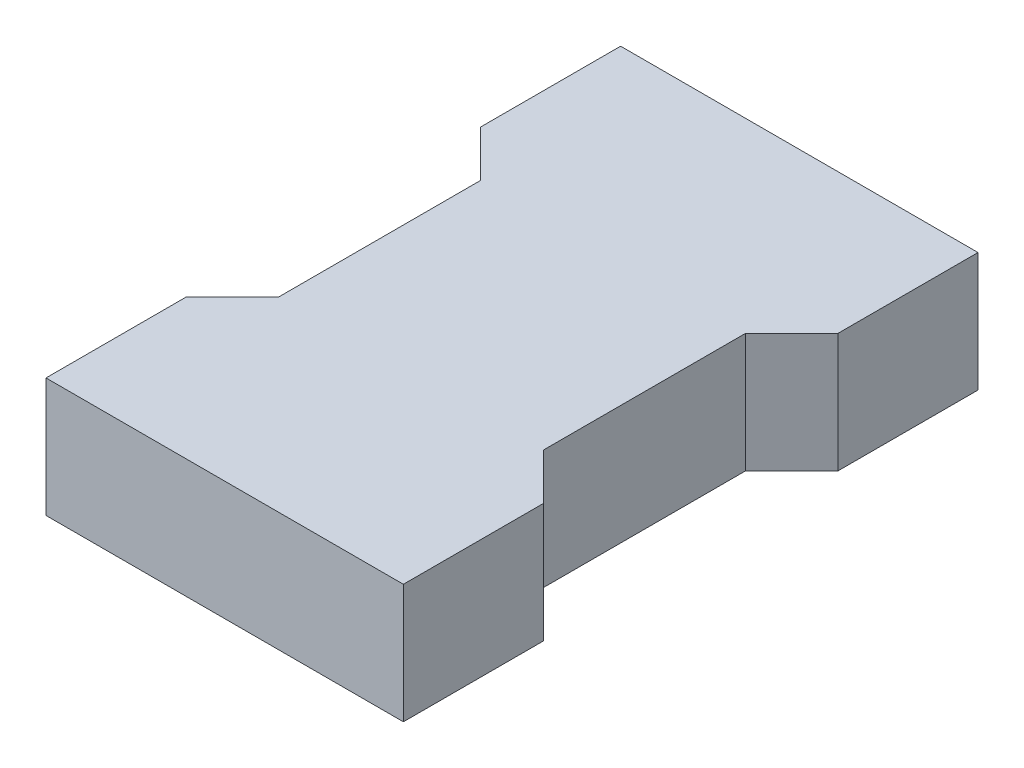
SolidWorks part; units mm, degrees
ref_plane "前视基准面" through (0, 0, 0) normal (0, 0, 1) x (1, 0, 0)
ref_plane "上视基准面" through (0, 0, 0) normal (0, 1, 0) x (1, 0, 0)
ref_plane "右视基准面" through (0, 0, 0) normal (1, 0, 0) x (0, 0, -1)
sketch "草图1" plane through (0, 0, 0) normal (0, 1, 0) x (1, 0, 0)
  line L0 (-25.5, 21) -> (-18.9026, 14.4026)
  line L1 (-25.5, 41) -> (25.5, 41)
  line L2 (-25.5, 41) -> (-25.5, 21)
  line L3 (-25.5, -41) -> (25.5, -41)
  line L4 (25.5, 41) -> (25.5, 21)
  line L5 (-25.5, 41) -> (25.5, -41) construction
  line L6 (-25.5, -41) -> (25.5, 41) construction
  line L7 (-18.9026, 14.4026) -> (-18.9026, -14.4026)
  line L8 (-18.9026, -14.4026) -> (-25.5, -21)
  line L9 (0, 53.9342) -> (0, -53.269) construction
  line L10 (18.9026, -14.4026) -> (25.5, -21)
  line L11 (25.5, 21) -> (18.9026, 14.4026)
  line L12 (18.9026, 14.4026) -> (18.9026, -14.4026)
  line L13 (-25.5, -21) -> (-25.5, -41)
  line L14 (25.5, -21) -> (25.5, -41)
  point P0 (0, 0)
  dimension "D1" = 51
  dimension "D2" = 82
  dimension "D3" = 20
  dimension "D4" = 20
  dimension "D5" = 45
extrude "凸台-拉伸1" add sketch "草图1" along normal blind 17
